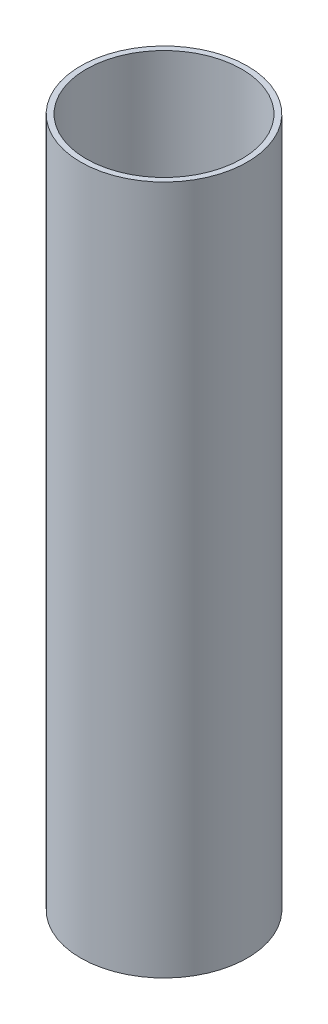
SolidWorks part; units mm, degrees
material "Fuzed Silica"
ref_plane "Front Plane" through (0, 0, 0) normal (0, 0, 1) x (1, 0, 0)
ref_plane "Top Plane" through (0, 0, 0) normal (0, 1, 0) x (1, 0, 0)
ref_plane "Right Plane" through (0, 0, 0) normal (1, 0, 0) x (0, 0, -1)
sketch "Sketch1" plane through (0, 0, 0) normal (0, 1, 0) x (1, 0, 0)
  circle A0 centre (0, 0) radius 35
  circle A1 centre (0, 0) radius 37.5
  dimension "D1" = 75
  dimension "D2" = 70
extrude "Boss-Extrude1" add sketch "Sketch1" along normal blind 310.2
